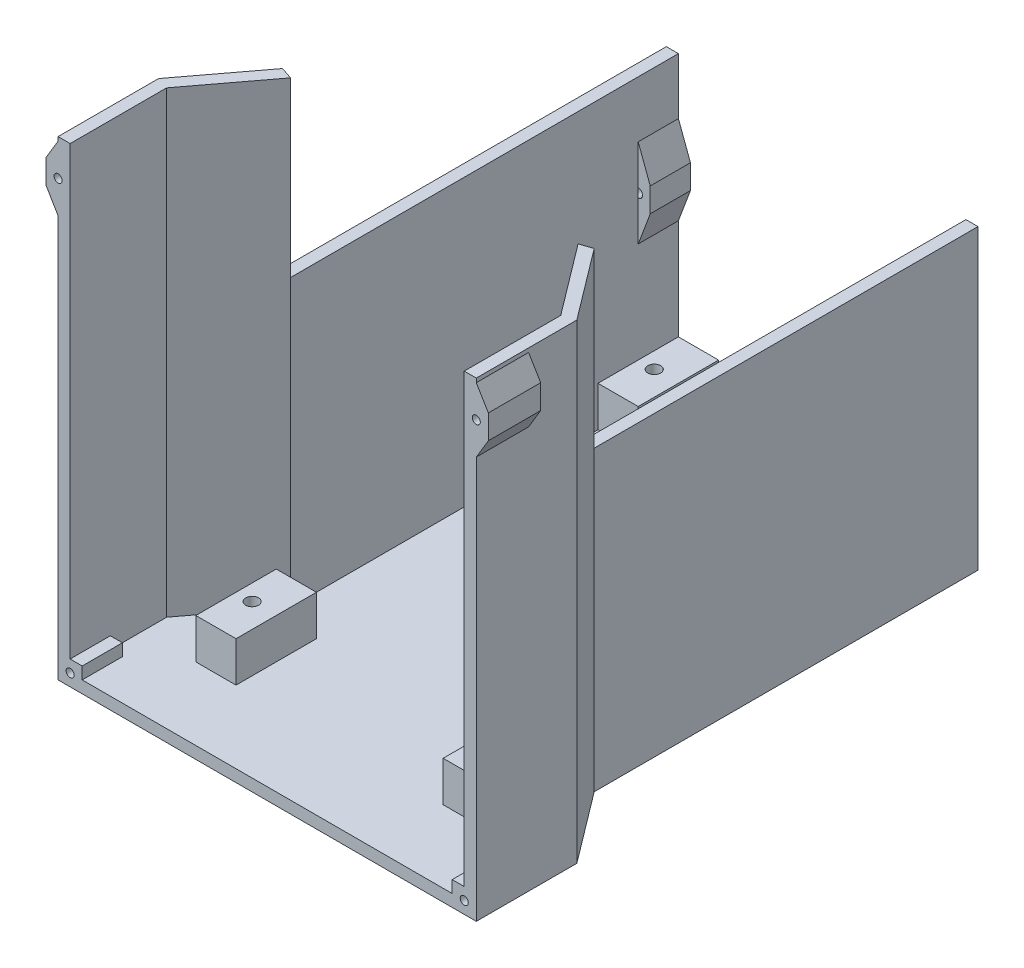
SolidWorks part; units mm, degrees
ref_plane "Płaszczyzna przednia" through (0, 0, 0) normal (0, 0, 1) x (1, 0, 0)
ref_plane "Płaszczyzna górna" through (0, 0, 0) normal (0, 1, 0) x (1, 0, 0)
ref_plane "Płaszczyzna prawa" through (0, 0, 0) normal (1, 0, 0) x (0, 0, -1)
sketch "Szkic1" plane through (0, 0, 0) normal (0, 1, 0) x (1, 0, 0)
  line L0 (3, 0) -> (3, 23.9953)
  line L1 (90.75, 138) -> (90.75, 42.5624)
  line L2 (77.75, 18) -> (87.75, 18)
  line L3 (52, -17.2217) -> (52, 169.3835) construction
  line L4 (56, 112) -> (48, 112)
  line L5 (56, 112) -> (56, 104)
  line L6 (56, 104) -> (48, 104)
  line L7 (48, 112) -> (48, 104)
  line L8 (13.25, 138) -> (13.25, 42.5624)
  line L9 (16.25, 41.5576) -> (3, 23.9953)
  line L10 (87.75, 138) -> (87.75, 41.5576)
  line L11 (26.25, 138) -> (77.75, 138)
  line L12 (16.25, 138) -> (16.25, 41.5576)
  line L13 (13.25, 42.5624) -> (0, 25)
  line L14 (22.25, 118) -> (22.25, 38) construction
  line L15 (26.25, 18) -> (16.25, 18)
  line L16 (16.25, 41.5576) -> (16.25, 18)
  line L17 (0, 0) -> (0, 25)
  line L18 (87.75, 41.5576) -> (87.75, 18)
  line L19 (87.75, 138) -> (87.75, 41.5576)
  line L21 (90.75, 42.5624) -> (104, 25)
  line L22 (87.75, 41.5576) -> (101, 23.9953)
  line L23 (104, 0) -> (104, 25)
  line L24 (101, 0) -> (101, 23.9953)
  line L25 (-6.798, 108) -> (125.7716, 108) construction
  line L26 (81.75, 118) -> (81.75, 38)
  line L27 (16.25, 18) -> (16.25, 41.5576)
  line L28 (22.25, 38) -> (22.25, 118)
  line L29 (87.75, 138) -> (77.75, 138)
  line L30 (26.25, 138) -> (16.25, 138)
  line L31 (87.75, 41.5576) -> (87.75, 138)
  line L32 (3, 0) -> (0, 0)
  line L33 (101, 0) -> (104, 0)
  line L34 (87.75, 18) -> (87.75, 41.5576)
  line L35 (3, 0) -> (104, 0)
  line L36 (77.75, 118) -> (87.75, 118)
  line L37 (16.25, 138) -> (13.25, 138)
  line L38 (87.75, 138) -> (90.75, 138)
  line L39 (26.25, 18) -> (26.25, 38)
  line L40 (26.25, 38) -> (16.25, 38)
  line L42 (77.75, 18) -> (77.75, 38)
  line L43 (77.75, 38) -> (81.75, 38)
  line L44 (26.25, 138) -> (26.25, 118)
  line L45 (26.25, 118) -> (16.25, 118)
  line L46 (77.75, 138) -> (77.75, 118)
  line L49 (81.75, 38) -> (87.75, 38)
  line L51 (77.75, 138) -> (26.25, 138)
  point P30 (52, 104)
  point P32 (48, 108)
  point P35 (101, 11.9976)
  dimension "D2" = 8
  dimension "D3" = 6
  dimension "D4" = 25
  dimension "D5" = 22
  dimension "D6" = 138
  dimension "D7" = 86
  dimension "D8" = 77.5
  dimension "D9" = 120
  dimension "D10" = 3
  dimension "D11" = 3
  dimension "D12" = 3
  dimension "D13" = 22
  dimension "D14" = 10
  dimension "D15" = 20
  dimension "D16" = 142.967
  dimension "D17" = 10
  dimension "D18" = 20
  dimension "D19" = 10
  dimension "D20" = 10
  dimension "D21" = 20
  dimension "D22" = 26
  dimension "D23" = 104
extrude "Dodanie-wyciągnięcie1" add sketch "Szkic1" against normal blind 3 contours L12 L37 L8 L13 L17 L32 L0 L9 | L45 L44 L30 L12 | L28 L45 L12 L16 L40 | L46 L11 L44 L45 L28 L40 L39 L15 L27 L16 L9 L0 L35 L24 L22 L18 L34 L2 L42 L43 L26 L36 L7 L4 L5 L6 | L29 L46 L36 L10 | L26 L49 L18 L31 L36 | L38 L10 L31 L22 L24 L33 L23 L21 L1 | L39 L40 L27 L15 | L49 L43 L42 L2 L34 region at (1.5, 0, -1.3895) region at (52, 0, -61.8528) region at (102.3895, 0, -11.9976) region at (19.25, 0, -78) region at (21.25, 0, -128) region at (21.25, 0, -28) region at (84.75, 0, -78) region at (82.75, 0, -128) region at (82.75, 0, -28)
extrude "Dodanie-wyciągnięcie2" add sketch "Szkic1<3>" along normal blind 71 contours L24 L33 L23 L21 L1 L8 L13 L17 L32 L0 L9 L12 L11 L10 L22 | L38 L10 L31 L22 L24 L33 L23 L21 L1 region at (1.5, 0, -1.3895) region at (102.3895, 0, -11.9976)
sketch "Szkic1<3>" plane through (0, 0, 0) normal (0, 1, 0) x (1, 0, 0) same geometry as "Szkic1"
sketch "Szkic2" plane through (0, 71, 0) normal (0, 1, 0) x (1, 0, 0)
  line L0 (87.75, 41.5576) -> (90.75, 42.5624)
  line L12 (90.75, 138) -> (87.75, 138)
  line L13 (87.75, 138) -> (87.75, 41.5576)
  line L14 (87.75, 41.5576) -> (101, 23.9953)
  line L15 (101, 23.9953) -> (101, 0)
  line L28 (101, 0) -> (104, 0)
  line L30 (104, 0) -> (104, 25)
  line L31 (13.25, 42.5624) -> (0, 25) construction
  line L32 (0, 25) -> (0, 0) construction
  line L33 (0, 0) -> (3, 0) construction
  line L34 (3, 0) -> (3, 23.9953) construction
  line L35 (3, 23.9953) -> (16.25, 41.5576) construction
  line L48 (13.25, 42.5624) -> (0, 25)
  line L49 (0, 25) -> (0, 0)
  line L50 (0, 0) -> (3, 0)
  line L51 (3, 0) -> (3, 23.9953)
  line L52 (3, 23.9953) -> (16.25, 41.5576)
  line L53 (13.25, 42.5624) -> (16.25, 41.5576)
  line L54 (104, 25) -> (90.75, 42.5624)
  line L55 (90.75, 42.5624) -> (90.75, 138)
  line L58 (87.75, 41.5576) -> (101, 23.9953)
  line L59 (101, 23.9953) -> (101, 0)
  line L60 (101, 0) -> (104, 0)
  line L61 (104, 0) -> (104, 25)
  line L62 (104, 25) -> (90.75, 42.5624)
  line M12 (13.25, 42.5624) -> (0, 25)
  line M13 (0, 25) -> (0, 0)
  line M14 (0, 0) -> (3, 0)
  line M15 (3, 0) -> (3, 23.9953)
  line M16 (3, 23.9953) -> (16.25, 41.5576)
  dimension "D1" = 0
extrude "Dodanie-wyciągnięcie4" add sketch "Szkic2" along normal blind 43 contours M12 M13 M14 M15 M16 | L61 L62 L0 L58 L59 L60 region at (14.6053, 71, -41.628)
extrude "Dodanie-wyciągnięcie5" add sketch "Szkic1<5>" along normal blind 10 contours L39 L40 L27 L15 | L49 L43 L42 L2 L34 | L45 L44 L30 L12 | L29 L46 L36 L10 region at (21.25, 0, -128) region at (21.25, 0, -28) region at (82.75, 0, -128) region at (82.75, 0, -28)
sketch "Szkic1<5>" plane through (0, 0, 0) normal (0, 1, 0) x (1, 0, 0) same geometry as "Szkic1"
sketch "Szkic3" plane through (0, 0, -138) normal (0, 0, -1) x (-1, 0, 0)
  line L0 (-90.75, 49) -> (-84.75, 49)
  line L1 (-90.75, 43) -> (-84.75, 43)
  line L2 (-84.75, 43) -> (-84.75, 49)
  line L3 (-52, 22.9971) -> (-52, 28.9971) construction
  line L4 (-90.75, 49) -> (-84.75, 49)
  line L5 (-90.75, 49) -> (-90.75, 43)
  line L6 (-13.25, 49) -> (-13.25, 43)
  line L7 (-13.25, 43) -> (-19.25, 43)
  line L8 (-19.25, 43) -> (-19.25, 49)
  line L9 (-13.25, 49) -> (-19.25, 49)
  line L10 (-90.75, 3) -> (-84.75, 3)
  line L11 (-90.75, -3) -> (-84.75, -3)
  line L12 (-84.75, -3) -> (-84.75, 3)
  line L13 (-52, 3.8613) -> (-52, 9.8613) construction
  line L14 (-90.75, 3) -> (-84.75, 3)
  line L15 (-90.75, 3) -> (-90.75, -3)
  line L16 (-13.25, 3) -> (-13.25, -3)
  line L17 (-13.25, -3) -> (-19.25, -3)
  line L18 (-19.25, -3) -> (-19.25, 3)
  line L19 (-13.25, 3) -> (-19.25, 3)
  line L20 (-90.75, -3) -> (-90.75, 71) construction
  line L21 (-13.25, -3) -> (-13.25, 71) construction
  line L22 (-90.75, -3) -> (-90.75, 71) construction
  line L23 (-13.25, -3) -> (-13.25, 71) construction
  line L24 (-90.75, -3) -> (-13.25, -3) construction
  line L25 (-84.75, 43) -> (-87.75, 35.5838)
  line L26 (-87.75, 71) -> (-87.75, 10) construction
  line L27 (-19.25, 43) -> (-16.25, 35)
  line L28 (-16.25, 71) -> (-16.25, 10) construction
  line L29 (-84.75, 49) -> (-87.75, 56.4162)
  line L30 (-19.25, 49) -> (-16.25, 57)
  circle A0 centre (-87.75, 46) radius 1.1
  circle A1 centre (-16.25, 46) radius 1.1
  circle A2 centre (-87.75, 0) radius 1.1
  circle A3 centre (-16.25, 0) radius 1.1
  line M10 (-87.75, 10) -> (-87.75, 71)
  line M16 (-16.25, 71) -> (-16.25, 10)
  dimension "D1" = 2.2
  dimension "D5" = 2.2
  dimension "D2" = 3
  dimension "D3" = 3
  dimension "D4" = 3
  dimension "D6" = 3
  dimension "D7" = 3
  dimension "D8" = 3
  dimension "D9" = 40
  dimension "D10" = 8
  dimension "D11" = 8
extrude "Dodanie-wyciągnięcie6" add sketch "Szkic3" against normal blind 10 separate body contours A0 L1 L2 L0 M10 | A0 M10 | A1 L9 L8 L7 M16 | A1 M16 | L25 L1 M10 | L7 L27 M16 | L30 L9 M16 | L0 L29 M10 region at (86.75, 51.4721, -138) region at (86.128, 46, -138) region at (87.2831, 46, -138) region at (86.75, 40.5279, -138) region at (17.872, 46, -138) region at (17.25, 51.6667, -138) region at (17.25, 40.3333, -138) region at (16.7169, 46, -138)
sketch "Szkic4" plane through (0, 0, 0) normal (0, 0, 1) x (1, 0, 0)
  line L0 (-3, 108) -> (3, 108)
  line L1 (-3, 102) -> (3, 102)
  line L2 (3, 102) -> (3, 108)
  line L3 (-3, 108) -> (3, 108)
  line L4 (-3, 108) -> (-3, 102)
  line L5 (107, 108) -> (107, 102)
  line L10 (107, 102) -> (101, 102)
  line L11 (52, 6.2492) -> (52, -121.2067) construction
  line L12 (101, 102) -> (101, 108)
  line L13 (107, 108) -> (101, 108)
  line L14 (0, 3) -> (6, 3)
  line L15 (0, -3) -> (6, -3)
  line L20 (6, -3) -> (6, 3)
  line L21 (52, 121.2067) -> (52, 45.8783) construction
  line L22 (0, 3) -> (6, 3)
  line L23 (0, 3) -> (0, -3)
  line L24 (104, 3) -> (104, -3)
  line L25 (104, -3) -> (98, -3)
  line L26 (98, -3) -> (98, 3)
  line L28 (104, 3) -> (98, 3)
  line L30 (104, -3) -> (104, 114) construction
  line L31 (104, -3) -> (0, -3) construction
  line L32 (3, 114) -> (3, 0) construction
  line L33 (-3, 102) -> (0, 96.9895)
  line L34 (0, -3) -> (0, 114) construction
  line L35 (-3, 108) -> (0, 113.0105)
  line L36 (107, 108) -> (104, 113.0105)
  line L37 (107, 102) -> (104, 96.9895)
  circle A4 centre (3, 0) radius 1
  circle A5 centre (101, 0) radius 1
  circle A6 centre (0, 105) radius 1
  circle A7 centre (104, 105) radius 1
  line M14 (104, -3) -> (104, 114)
  line M16 (101, 114) -> (101, 0)
  line M17 (101, 0) -> (3, 0)
  line M18 (3, 0) -> (3, 114)
  line M20 (0, 114) -> (0, -3)
  dimension "D1" = 2
  dimension "D5" = 92
  dimension "D6" = 2
  dimension "D13" = 2
  dimension "D2" = 3
  dimension "D3" = 3
  dimension "D4" = 3
  dimension "D7" = 3
  dimension "D8" = 3
  dimension "D9" = 3
  dimension "D10" = 99
  dimension "D11" = 99
  dimension "D12" = 5.84
extrude "Dodanie-wyciągnięcie7" add sketch "Szkic4" against normal blind 10 contours A6 M18 | A6 L1 L2 M18 | L1 M18 | M18 | M16 | L12 M16 | M16 | M16 | A4 L20 M17 M18 | A5 L28 L26 M17 M16 | A4 M17 M18 | M16 | L1 M18 | A6 L0 L4 L1 M20 | A7 L10 L5 L13 M14 | L35 L0 M20 | L37 L10 M14 | L13 L36 M14 | A5 region at (-1, 109.6702, 0) region at (-1.6028, 105, 0) region at (99.3972, 1.6028, 0) region at (1.6028, 105, 0) region at (-1, 100.3298, 0) region at (-0.4244, 105, 0) region at (4.6028, 1.6028, 0) region at (3.4244, 0.4244, 0) region at (100.5756, 0.4244, 0) region at (105, 100.3298, 0) region at (105.6028, 105, 0) region at (105, 109.6702, 0)
extrude "Wytnij-wyciągnięcie1" cut sketch "Szkic4<5>" against normal up to surface (10 mm away) contours A4 M17 M18 | A4 M18 M17 | A5 M17 M16 | A5 M16 M17 | A7 M14 | A6 region at (2.8585, -0.1415, 0) region at (3.4244, 0.4244, 0) region at (101.1415, -0.1415, 0) region at (100.5756, 0.4244, 0) region at (103.5756, 105, 0) up to face at (99.5, 1.5, -10)
sketch "Szkic4<5>" plane through (0, 0, 0) normal (0, 0, 1) x (1, 0, 0) same geometry as "Szkic4"
extrude "Wytnij-wyciągnięcie2" cut sketch "Szkic3<3>" against normal up to surface (10 mm away) contours A0 M10 | A0 M10 | A1 M16 | A1 M16 | A2 | A3 region at (88.2169, 46, -138) region at (87.2831, 46, -138) region at (16.7169, 46, -138) region at (15.7831, 46, -138) region at (87.75, 0, -138) region at (16.25, 0, -138) up to face at (17.75, 46, -128)
sketch "Szkic3<3>" plane through (0, 0, -138) normal (0, 0, -1) x (-1, 0, 0) same geometry as "Szkic3"
sketch "Szkic11" plane through (0, 0, -10) normal (0, 0, -1) x (-1, 0, 0)
  line L0 (0, 113.0105) -> (0, 106) construction
  line L1 (0, 104) -> (0, 96.9895) construction
  line L2 (0, 96.9895) -> (3, 102) construction
  line L3 (3, 102) -> (3, 108) construction
  line L4 (3, 108) -> (0, 113.0105) construction
  line L5 (-104, 106) -> (-104, 113.0105) construction
  line L6 (-104, 113.0105) -> (-107, 108) construction
  line L7 (-107, 108) -> (-107, 102) construction
  line L8 (-107, 102) -> (-104, 96.9895) construction
  line L9 (-104, 96.9895) -> (-104, 104) construction
  line L10 (0, 113.0105) -> (0, 106)
  line L11 (0, 104) -> (0, 96.9895)
  line L12 (0, 96.9895) -> (3, 102)
  line L13 (3, 102) -> (3, 108)
  line L14 (3, 108) -> (0, 113.0105)
  line L15 (-104, 106) -> (-104, 113.0105)
  line L16 (-104, 113.0105) -> (-107, 108)
  line L17 (-107, 108) -> (-107, 102)
  line L18 (-107, 102) -> (-104, 96.9895)
  line L19 (-104, 96.9895) -> (-104, 104)
  line L20 (0, 104) -> (0, 106)
  line L21 (-104, 104) -> (-104, 106)
extrude "Dodanie-wyciągnięcie11" add sketch "Szkic11" along normal blind 3
sketch "Szkic12" plane through (0, 10, 0) normal (0, 1, 0) x (1, 0, 0)
  line L0 (87.75, 38) -> (77.75, 38) construction
  line L1 (77.75, 38) -> (77.75, 18) construction
  line L2 (77.75, 18) -> (87.75, 18) construction
  line L3 (87.75, 18) -> (87.75, 38) construction
  line L4 (26.25, 18) -> (26.25, 38) construction
  line L5 (26.25, 38) -> (16.25, 38) construction
  line L6 (16.25, 38) -> (16.25, 18) construction
  line L7 (16.25, 18) -> (26.25, 18) construction
  line L8 (87.75, 138) -> (77.75, 138) construction
  line L9 (77.75, 138) -> (77.75, 118) construction
  line L10 (77.75, 118) -> (87.75, 118) construction
  line L11 (87.75, 118) -> (87.75, 138) construction
  line L12 (16.25, 118) -> (26.25, 118) construction
  line L13 (26.25, 118) -> (26.25, 138) construction
  line L14 (26.25, 138) -> (16.25, 138) construction
  line L15 (16.25, 138) -> (16.25, 118) construction
  line L16 (87.75, 38) -> (77.75, 38)
  line L17 (77.75, 38) -> (77.75, 18)
  line L18 (77.75, 18) -> (87.75, 18)
  line L19 (87.75, 18) -> (87.75, 38)
  line L20 (26.25, 18) -> (26.25, 38)
  line L21 (26.25, 38) -> (16.25, 38)
  line L22 (16.25, 38) -> (16.25, 18)
  line L23 (16.25, 18) -> (26.25, 18)
  line L24 (87.75, 138) -> (77.75, 138)
  line L25 (77.75, 138) -> (77.75, 118)
  line L26 (77.75, 118) -> (87.75, 118)
  line L27 (87.75, 118) -> (87.75, 138)
  line L28 (16.25, 118) -> (26.25, 118)
  line L29 (26.25, 118) -> (26.25, 138)
  line L30 (26.25, 138) -> (16.25, 138)
  line L31 (16.25, 138) -> (16.25, 118)
  line L32 (52, 138) -> (52, 18) construction
  line L33 (77.75, 138) -> (26.25, 138) construction
  line L34 (52, 78) -> (10.8876, 78) construction
  line L35 (10.8876, 78) -> (92.4044, 78) construction
  circle A0 centre (20.25, 128) radius 1.6
  circle A1 centre (83.75, 128) radius 1.6
  circle A2 centre (83.75, 28) radius 1.6
  circle A3 centre (20.25, 28) radius 1.6
  dimension "D1" = 3.2
  dimension "D2" = 4
  dimension "D3" = 10
  dimension "D4" = 10
extrude "Wytnij-wyciągnięcie3" cut sketch "Szkic12" against normal up to surface (13 mm away) contours A3 | A2 | A0 | A1 region at (20.25, 10, -128) region at (83.75, 10, -28) region at (20.25, 10, -28) up to face at (52, -3, -51.3906)
chamfer "Sfazowanie2" distance 1 angle 45 4 edges at (83.75, -3, -126.4) (20.25, -3, -126.4) (20.25, -3, -26.4) (83.75, -3, -26.4)
